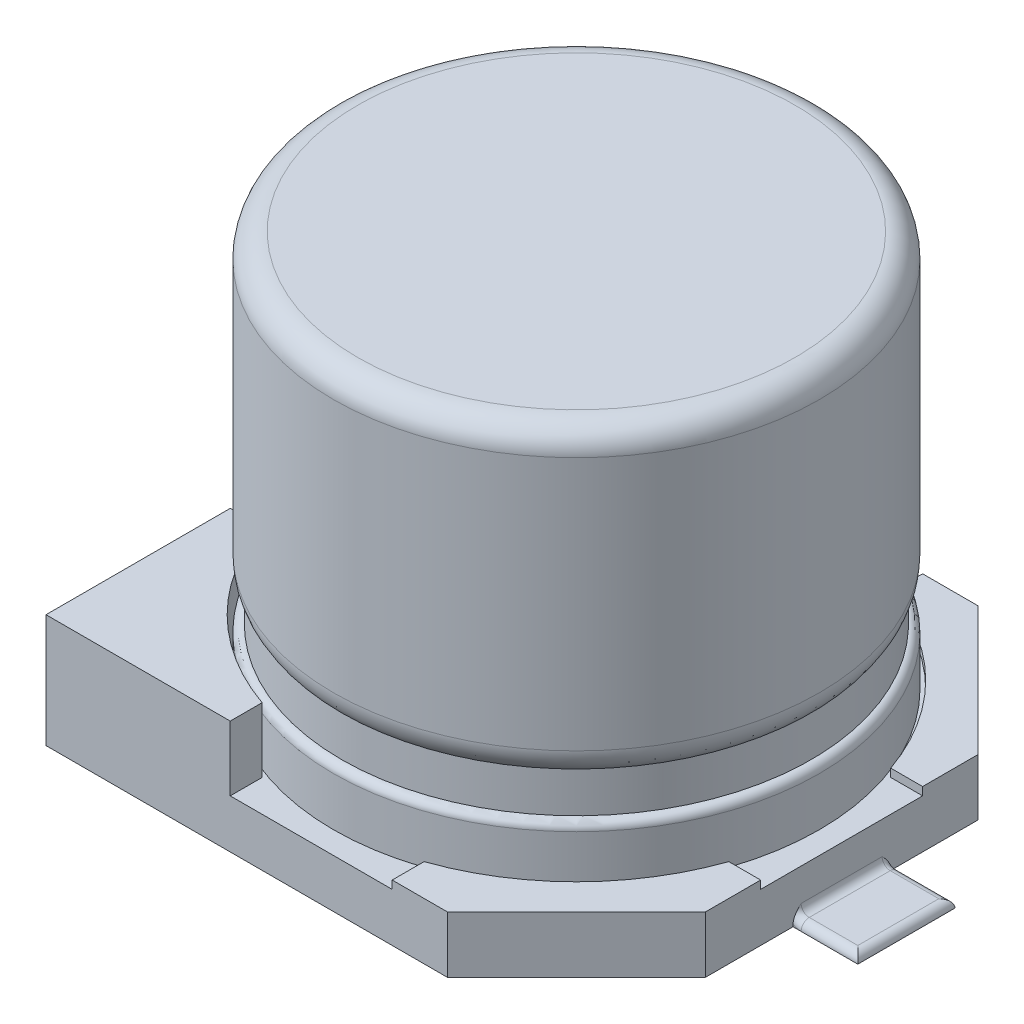
SolidWorks part; units mm, degrees
ref_plane "Plan de face" through (0, 0, 0) normal (0, 0, 1) x (1, 0, 0)
ref_plane "Plan de dessus" through (0, 0, 0) normal (0, 1, 0) x (1, 0, 0)
ref_plane "Plan de droite" through (0, 0, 0) normal (1, 0, 0) x (0, 0, -1)
sketch "Esquisse1" plane through (0, 0, 0) normal (0, 1, 0) x (1, 0, 0)
  line L0 (4.959, 6.55) -> (6.55, 4.959)
  line L1 (0, 0) -> (4.959, 0)
  line L2 (0, 0) -> (0, 6.55)
  line L3 (0, 6.55) -> (4.959, 6.55)
  line L4 (6.55, 1.591) -> (6.55, 4.959)
  line L5 (6.55, 1.591) -> (4.959, 0)
  dimension "D1" = 6.55
  dimension "D2" = 2.25
  dimension "D3" = 45
  dimension "D4" = 45
  dimension "D5" = 6.55
extrude "Boss.-Extru.1" add sketch "Esquisse1" along normal blind 0.7
sketch "Esquisse2" plane through (0, 0.7, 0) normal (0, 1, 0) x (1, 0, 0)
  line L0 (0, 3.275) -> (6.55, 3.275) construction
  line L1 (0, 6.55) -> (0, 0) construction
  line L2 (6.55, 1.591) -> (6.55, 4.959) construction
  line L3 (3.275, 3.275) -> (3.275, 6.55) construction
  line L4 (4.959, 6.55) -> (0, 6.55) construction
  line L5 (3.275, 3.275) -> (3.275, 0) construction
  line L6 (0, 0) -> (4.959, 0) construction
  line L7 (0, 3.275) -> (0.3936, 3.275) construction
  line L8 (2.275, 6.55) -> (4.275, 6.55)
  line L9 (2.275, 6.55) -> (2.275, 6.1564)
  line L10 (6.1564, 3.275) -> (6.55, 3.275) construction
  line L11 (4.275, 6.55) -> (4.275, 6.1564)
  line L12 (0, 2.275) -> (0.3936, 2.275)
  line L13 (0, 2.275) -> (0, 4.275)
  line L14 (0, 4.275) -> (0.3936, 4.275)
  line L15 (6.55, 2.275) -> (6.1564, 2.275)
  line L16 (3.275, 0.3936) -> (3.275, 0) construction
  line L17 (2.275, 0) -> (4.275, 0)
  line L18 (2.275, 0) -> (2.275, 0.3936)
  line L19 (6.55, 2.275) -> (6.55, 4.275)
  line L20 (4.275, 0) -> (4.275, 0.3936)
  line L21 (6.55, 4.275) -> (6.1564, 4.275)
  arc A0 (0.3936, 2.275) -> (2.275, 0.3936) centre (3.275, 3.275) ccw
  arc A1 (2.275, 6.1564) -> (0.3936, 4.275) centre (3.275, 3.275) ccw
  arc A2 (4.275, 0.3936) -> (6.1564, 2.275) centre (3.275, 3.275) ccw
  arc A3 (6.1564, 4.275) -> (4.275, 6.1564) centre (3.275, 3.275) ccw
  point P18 (3.275, 6.1564)
  point P25 (0.1968, 3.275)
  point P32 (3.275, 0.1968)
  point P38 (6.3532, 3.275)
  dimension "D1" = 6.1
  dimension "D2" = 2
  dimension "D3" = 2
  dimension "D4" = 2
  dimension "D5" = 2
extrude "Enlèv. mat.-Extru.1" cut sketch "Esquisse2" against normal blind 0.1
sketch "Esquisse3" plane through (0, 0.7, 0) normal (0, 1, 0) x (1, 0, 0)
  line L0 (0, 0) -> (2.275, 0) construction
  line L1 (2.275, 0) -> (2.275, 0.3936) construction
  line L2 (0.3936, 2.275) -> (0, 2.275) construction
  line L3 (0, 2.275) -> (0, 0) construction
  line L4 (0, 6.55) -> (0, 4.275) construction
  line L5 (0, 4.275) -> (0.3936, 4.275) construction
  line L6 (2.275, 6.1564) -> (2.275, 6.55) construction
  line L7 (2.275, 6.55) -> (0, 6.55) construction
  line L8 (0, 0) -> (2.275, 0)
  line L9 (2.275, 0) -> (2.275, 0.3936)
  line L10 (0.3936, 2.275) -> (0, 2.275)
  line L11 (0, 2.275) -> (0, 0)
  line L12 (0, 6.55) -> (0, 4.275)
  line L13 (0, 4.275) -> (0.3936, 4.275)
  line L14 (2.275, 6.1564) -> (2.275, 6.55)
  line L15 (2.275, 6.55) -> (0, 6.55)
  arc A0 (0.3936, 2.275) -> (2.275, 0.3936) centre (3.275, 3.275) ccw construction
  arc A1 (2.275, 6.1564) -> (0.3936, 4.275) centre (3.275, 3.275) ccw construction
  arc A2 (0.3936, 2.275) -> (2.275, 0.3936) centre (3.275, 3.275) ccw
  arc A3 (2.275, 6.1564) -> (0.3936, 4.275) centre (3.275, 3.275) ccw
extrude "Boss.-Extru.2" add sketch "Esquisse3" along normal blind 0.7
sketch "Esquisse4" plane through (0, 0.6, 0) normal (0, 1, 0) x (1, 0, 0)
  circle A0 centre (3.275, 3.275) radius 3
  dimension "D1" = 6
extrude "Boss.-Extru.3" add sketch "Esquisse4" along normal blind 0.7
fillet "Congé1" radius 0.1 1 edges at (3.275, 1.3, -0.275)
sketch "Esquisse5" plane through (0, 1.3, 0) normal (0, 1, 0) x (1, 0, 0)
  circle A1 centre (3.275, 3.275) radius 2.9
  circle A2 centre (3.275, 3.275) radius 2.9
  dimension "D1" = 0
extrude "Boss.-Extru.4" add sketch "Esquisse5" along normal blind 0.5
sketch "Esquisse6" plane through (0, 1.8, 0) normal (0, 1, 0) x (1, 0, 0)
  circle A0 centre (3.275, 3.275) radius 3 construction
  circle A1 centre (3.275, 3.275) radius 3
extrude "Boss.-Extru.5" add sketch "Esquisse6" along normal blind 3.7
fillet "Congé2" radius 0.4 1 edges at (3.275, 1.8, -0.275)
fillet "Congé3" radius 0.3 1 edges at (3.275, 5.5, -0.275)
sketch "Esquisse7" plane through (6.55, 0, 0) normal (1, 0, 0) x (0, 0, -1)
  line L0 (3.275, 0) -> (3.275, 0.6) construction
  line L1 (1.591, 0) -> (4.959, 0) construction
  line L2 (2.275, 0.6) -> (4.275, 0.6) construction
  line L3 (3.275, 0.1) -> (3.275, 0) construction
  line L4 (2.675, 0) -> (3.875, 0)
  line L5 (2.675, 0) -> (2.675, 0.1)
  line L6 (2.675, 0.1) -> (3.875, 0.1)
  line L7 (3.875, 0) -> (3.875, 0.1)
  point P12 (3.275, 0.05)
  dimension "D1" = 1.2
  dimension "D2" = 0.1
extrude "Boss.-Extru.6" add sketch "Esquisse7" along normal blind 0.8
fillet "Congé4" radius 0.1 1 edges at (6.55, 0.1, -3.275)
fillet "Congé5" radius 0.1 5 edges at (6.5793, 0.1293, -3.875) (6.5793, 0.1293, -2.675) (7.35, 0.1, -3.275) (7, 0.1, -3.875) (7, 0.1, -2.675)
sketch "Esquisse8" plane through (0, 0, 0) normal (-1, 0, 0) x (0, 0, 1)
  line L0 (-3.275, 0) -> (-3.275, 0.6) construction
  line L1 (-6.55, 0) -> (0, 0) construction
  line L2 (-4.275, 0.6) -> (-2.275, 0.6) construction
  line L3 (-3.275, 0.1) -> (-3.275, 0) construction
  line L4 (-3.875, 0.1) -> (-2.675, 0.1)
  line L5 (-3.875, 0.1) -> (-3.875, 0)
  line L6 (-3.875, 0) -> (-2.675, 0)
  line L7 (-2.675, 0.1) -> (-2.675, 0)
  point P12 (-3.275, 0.05)
  dimension "D1" = 1.2
  dimension "D2" = 0.1
extrude "Boss.-Extru.7" add sketch "Esquisse8" along normal blind 0.8
fillet "Congé6" radius 0.1 1 edges at (0, 0.1, -3.275)
fillet "Congé7" radius 0.1 5 edges at (-0.0293, 0.1293, -2.675) (-0.0293, 0.1293, -3.875) (-0.45, 0.1, -2.675) (-0.8, 0.1, -3.275) (-0.45, 0.1, -3.875)
